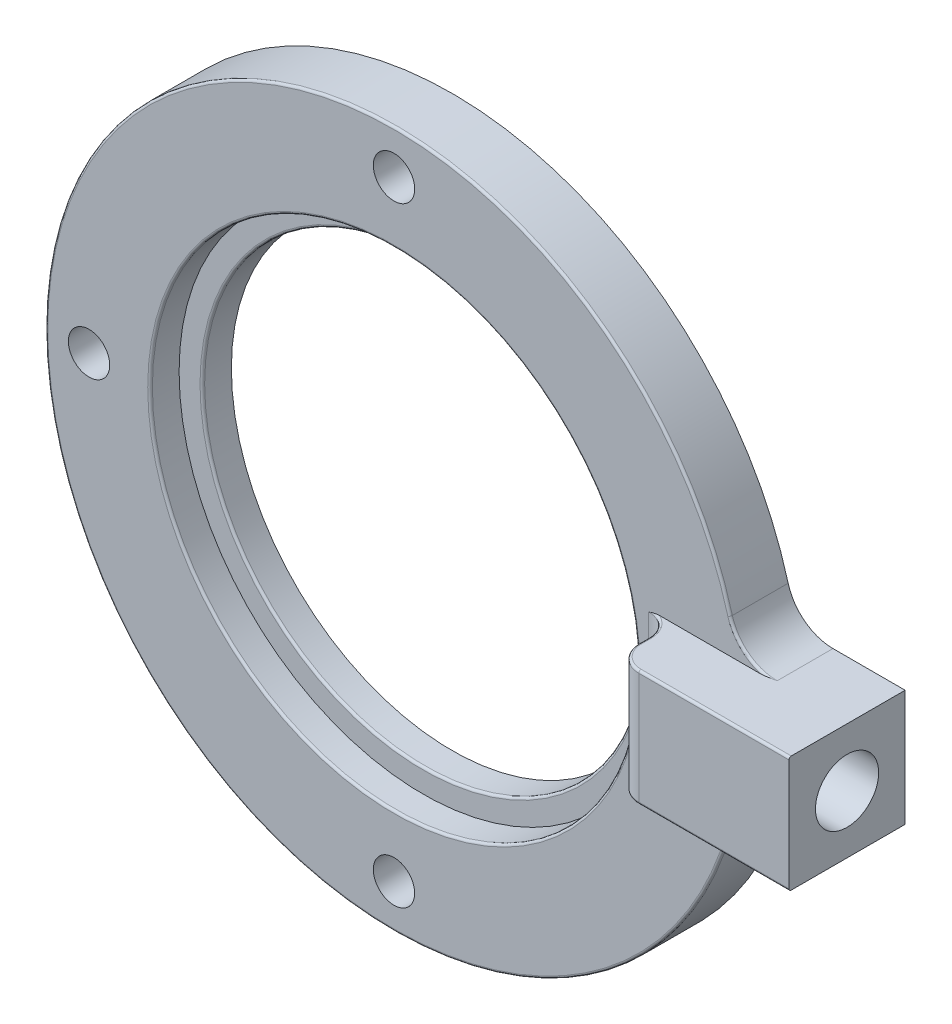
SolidWorks part; units mm, degrees
ref_plane "Front Plane" through (0, 0, 0) normal (0, 0, 1) x (1, 0, 0)
ref_plane "Top Plane" through (0, 0, 0) normal (0, 1, 0) x (1, 0, 0)
ref_plane "Right Plane" through (0, 0, 0) normal (1, 0, 0) x (0, 0, -1)
sketch "Sketch1" plane through (0, 0, 0) normal (0, 0, 1) x (1, 0, 0)
  circle A0 centre (0, 0) radius 19.05
  dimension "D1" = 38.1
extrude "Boss-Extrude1" add sketch "Sketch1" along normal blind 3.175
sketch "Sketch2" plane through (0, 0, 3.175) normal (0, 0, 1) x (1, 0, 0)
  circle A0 centre (0, 0) radius 12.065
  dimension "D1" = 24.13
extrude "Cut-Extrude1" cut sketch "Sketch2" against normal through all
sketch "Sketch3" plane through (0, 0, 3.175) normal (0, 0, 1) x (1, 0, 0)
  circle A0 centre (0, 0) radius 13.335
  dimension "D1" = 26.67
extrude "Cut-Extrude2" cut sketch "Sketch3" against normal offset from surface (1.5875 mm away) 1.5875 up to face at (12.065, 0, 0)
sketch "Sketch4" plane through (0, 0, 0) normal (1, 0, 0) x (0, 0, -1)
  line L0 (0, 0) -> (-3.175, 0) construction
  line L1 (-3.175, 19.05) -> (-3.175, -19.05) construction
  line L3 (0, -3.175) -> (-6.35, -3.175)
  line L4 (0, -3.175) -> (0, 3.175)
  line L5 (0, 3.175) -> (-6.35, 3.175)
  line L6 (-6.35, -3.175) -> (-6.35, 3.175)
  line L7 (0, -3.175) -> (-6.35, 3.175) construction
  line L8 (0, 3.175) -> (-6.35, -3.175) construction
  point P5 (-3.175, 0)
  dimension "D1" = 6.35
  dimension "D2" = 6.35
extrude "Boss-Extrude2" add sketch "Sketch4" along normal blind 9.525 from offset 15.24
fillet "Fillet1" radius 2.54 2 edges at (18.7836, 3.175, 1.5875) (18.7836, -3.175, 1.5875)
sketch "Sketch5" plane through (24.765, 0, 0) normal (1, 0, 0) x (0, 0, -1)
  line L0 (-6.35, 0) -> (0, 0) construction
  line L1 (-6.35, 3.175) -> (-6.35, -3.175) construction
  line L2 (0, -3.175) -> (0, 3.175) construction
  circle A0 centre (-3.175, 0) radius 1.7272
  dimension "D1" = 3.4544
extrude "Cut-Extrude3" cut sketch "Sketch5" against normal blind 7.62
fillet "Fillet2" radius 1.3208 2 edges at (15.24, 0, 6.35) (15.24, 0, 3.175)
fillet "Fillet3" radius 0.127 13 edges at (19.2798, 3.6952, 3.175) (19.2798, -3.6952, 3.175) (14.8531, -3.175, 3.5619) (15.24, -3.175, 4.7625) (15.6269, -3.175, 5.9631) (14.8531, 3.175, 3.5619) (15.24, 3.175, 4.7625) (15.6269, 3.175, 5.9631) (12.065, 0, 1.5875) (13.335, 0, 3.175) (-19.05, 0, 3.175) (20.6629, -3.175, 6.35) (20.6629, 3.175, 6.35)
sketch "Sketch6" plane through (0, 0, 3.175) normal (0, 0, 1) x (1, 0, 0)
  circle A0 centre (0, 0) radius 16.6687 construction
  circle A1 centre (-16.6687, 0) radius 1.1303
  circle A2 centre (0, 16.6687) radius 1.1303
  circle A3 centre (0, -16.6687) radius 1.1303
  dimension "D1" = 33.3375
  dimension "D2" = 2.2606
  dimension "D3" = 2.2606
  dimension "D4" = 2.2606
extrude "Cut-Extrude4" cut sketch "Sketch6" against normal through all
